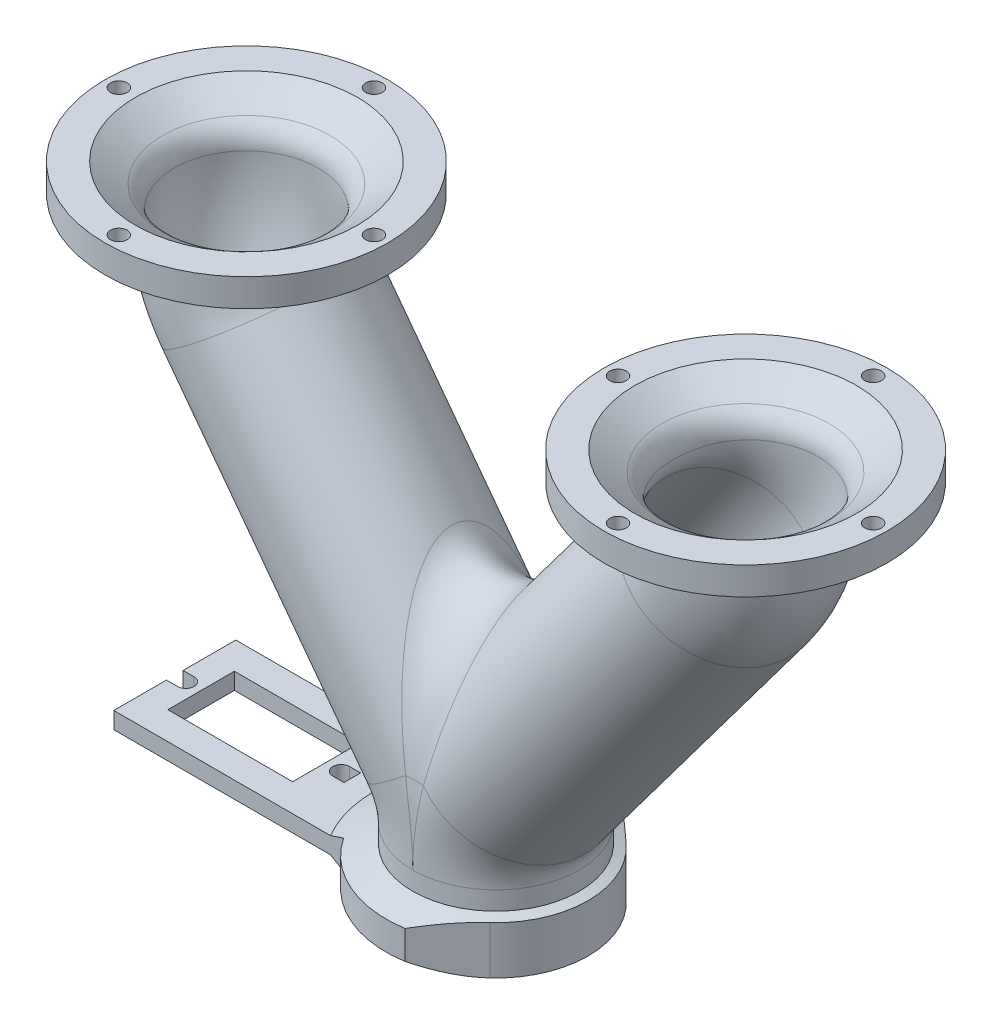
SolidWorks part; units mm, degrees
ref_plane "前视基准面" through (0, 0, 0) normal (0, 0, 1) x (1, 0, 0)
ref_plane "上视基准面" through (0, 0, 0) normal (0, 1, 0) x (1, 0, 0)
ref_plane "右视基准面" through (0, 0, 0) normal (1, 0, 0) x (0, 0, -1)
other "Configuration Table"
sketch "草图1" plane through (0, 0, 0) normal (0, 0, 1) x (1, 0, 0)
  line L0 (45, 0) -> (-45, 0) construction
  line L1 (-45, 0) -> (-45, 60) construction
  line L2 (-41, 54.6667) -> (-4, 5.3333)
  line L3 (-45, 66.6667) -> (-45, 74)
  line L4 (45, 0) -> (45, 60) construction
  line L5 (0, -6.6667) -> (0, -10)
  arc A0 (-45, 66.6667) -> (-41, 54.6667) centre (-25, 66.6667) ccw
  arc A1 (0, -6.6667) -> (-4, 5.3333) centre (-20, -6.6667) ccw
  point P13 (0, 0)
  dimension "D1" = 20
  dimension "D2" = 20
  dimension "D3" = 10
  dimension "D4" = 74
  dimension "D5" = 60
  dimension "D6" = 45
sweep "扫描2" add path "草图1" circular profile diameter 30 parameters "D3"=30
mirror "镜向5" about plane through (0, 0, 0) normal (1, 0, 0) of "扫描2"
sweep "切除-扫描4" cut path "草图1<4>" circular profile diameter 26 parameters "D3"=26
sketch "草图1<4>" plane through (0, 0, 0) normal (0, 0, 1) x (1, 0, 0) same geometry as "草图1"
mirror "镜向6" about plane through (0, 0, 0) normal (1, 0, 0) of "切除-扫描4"
sketch "草图127" plane through (0, 0, 0) normal (0, 0, 1) x (1, 0, 0)
  line L0 (0, -10) -> (0, -55)
  line L1 (-15, -10) -> (15, -10) construction
  line L4 (-13, -10) -> (-15, -10)
  line L8 (-8, -25.21) -> (-6, -25.21)
  line L10 (-21.821, -15.71) -> (-71.75, -15.71)
  line L11 (-71.75, -15.71) -> (-71.75, -12.71)
  line L12 (-71.75, -12.71) -> (-21.821, -12.71)
  line L13 (0, -55) -> (0, -25.21)
  line L14 (0, -25.21) -> (-6, -25.21)
  line L22 (-15, -10) -> (-21.821, -12.71)
  line L27 (-21.821, -15.71) -> (-8, -25.21)
  line L28 (-13, -10) -> (-6, -25.21)
  dimension "D1" = 9.5
  dimension "D2" = 15.21
  dimension "D3" = 2
  dimension "D4" = 3
  dimension "D5" = 6
revolve "旋转2" add sketch "草图127" angle 360 about L13 region at (-32.7905, -15.306, 0)
ref_plane "基准面1" through (0, -15.71, 0) normal (0, -1, 0) x (-1, 0, 0)
sketch "草图136" plane through (0, -15.71, 0) normal (0, -1, 0) x (-1, 0, 0)
  line L0 (25.92, 1.5) -> (25.92, -1.5)
  line L1 (30.67, 6) -> (30.67, -6)
  line L2 (25.92, 6) -> (57.92, 6)
  line L3 (25.92, 6) -> (25.92, 1.5)
  line L4 (25.92, -6) -> (57.92, -6)
  line L5 (57.92, 6) -> (57.92, 1.5)
  line L6 (25.92, 6) -> (57.92, -6) construction
  line L7 (25.92, -6) -> (57.92, 6) construction
  line L8 (53.17, 6) -> (53.17, -6)
  line L9 (57.92, -1.5) -> (57.92, -6)
  line L10 (27.92, -1.5) -> (25.92, -1.5)
  line L11 (27.92, 1.5) -> (25.92, 1.5)
  line L12 (55.92, -1.5) -> (57.92, -1.5)
  line L13 (55.92, 1.5) -> (57.92, 1.5)
  line L14 (57.92, 11) -> (16.4885, 11)
  line L15 (25.92, -1.5) -> (25.92, -6)
  line L16 (57.92, 7) -> (57.92, -7)
  line L17 (-3.18, 19.5642) -> (-11.1768, 12.2941)
  line L18 (57.92, 11) -> (57.92, 7)
  line L19 (57.92, -7) -> (57.92, -11)
  line L20 (57.92, -11) -> (16.4885, -11)
  line L21 (0, 0) -> (7.75, 0)
  line L22 (-3.18, -19.5642) -> (-11.1768, -12.2941)
  arc A0 (55.92, 1.5) -> (55.92, -1.5) centre (55.92, 0) ccw
  arc A1 (27.92, 1.5) -> (27.92, -1.5) centre (27.92, 0) cw
  circle A3 centre (0, 0) radius 7.75 construction
  circle A5 centre (0, 0) radius 71.75 construction
  circle A6 centre (0, 0) radius 71.75
  circle A10 centre (0, 0) radius 16.6152
  arc A12 (-3.18, -19.5642) -> (-3.18, 19.5642) centre (0, 0) ccw
  circle A13 centre (0, 0) radius 21.821 construction
  point P9 (41.92, 6)
  point P33 (57.92, 0)
  dimension "D6" = 5
  dimension "D10" = 2
  dimension "D1" = 32
  dimension "D2" = 12
  dimension "D3" = 11.25
  dimension "D4" = 11.25
  dimension "D5" = 57.92
  dimension "D7" = 5
extrude "切除-拉伸1" cut sketch "草图136" against normal mid plane 20 contours L8 L2 L1 L4 | A1 L11 L0 L10 | L13 A0 L12 L16 | A6 L18 L16 L5 L9 L19 L20 region at (-27.5267, -15.71, 0) region at (-41.92, -15.71, 0) region at (-56.3133, -15.71, 0) region at (69.7206, -15.71, 0)
ref_plane "基准面2" through (0, 74, 0) normal (0, 1, 0) x (1, 0, 0)
sketch "草图137" plane through (0, 74, 0) normal (0, 1, 0) x (1, 0, 0)
  circle A0 centre (-45, 0) radius 15 construction
  circle A1 centre (-45, 0) radius 15
  circle A2 centre (-45, 0) radius 12.3464
  circle A4 centre (-22, 0) radius 1.5
  circle A5 centre (-45, -23) radius 1.5
  circle A6 centre (-68, 0) radius 1.5
  circle A7 centre (-45, 23) radius 1.5
  circle A8 centre (-45, 0) radius 25.5
  point P16 (-45, 0)
  dimension "D1" = 4
  dimension "D2" = 23
extrude "凸台-拉伸1" add sketch "草图137" against normal blind 5 contours A2 A7 A6 A1 A4 A5 region at (-69.7788, 74, 0)
mirror "镜向7" about plane through (0, 0, 0) normal (1, 0, 0) of "凸台-拉伸1"
fillet "圆角3" radius 10 3 edges at (0, 25, 0)
sketch "草图174" plane through (0, 0, 0) normal (0, 0, 1) x (1, 0, 0)
  line L0 (-43.5, 69) -> (-70.5, 69)
  line L1 (-70.5, 69) -> (-70.5, 74)
  line L2 (28.05, 74) -> (-28.05, 74) construction
  line L3 (-70.5, 74) -> (-70.5, 69) construction
  line L6 (-45, 74) -> (-65, 74)
  line L11 (-45, 66.6667) -> (-45, 74)
  line L12 (-45, 74) -> (-62.8042, 74)
  line L13 (-65, 74) -> (-58, 69)
  line L14 (-60, 66.6667) -> (-30, 66.6667) construction
  line L15 (-63.0513, 69) -> (-61.0513, 69)
  line L16 (-45, 74) -> (-58, 74)
  line L17 (-58, 74) -> (-58, 69)
  line L18 (-58, 69) -> (-63.0513, 69)
  dimension "D1" = 20
  dimension "D2" = 2
  dimension "D3" = 13
revolve "切除-旋转3" cut sketch "草图174" angle 360 about L11 region at (-60.3333, 72.3333, 0)
mirror "镜向8" about plane through (0, 0, 0) normal (1, 0, 0) of "切除-旋转3"
fillet "圆角4" radius 5 2 edges at (-45, 69, -13) (45, 69, -13)
fillet "圆角5" radius 5 1 edges at (13, -10, 0)
equation "\"12.5.000000mm\"=10"
